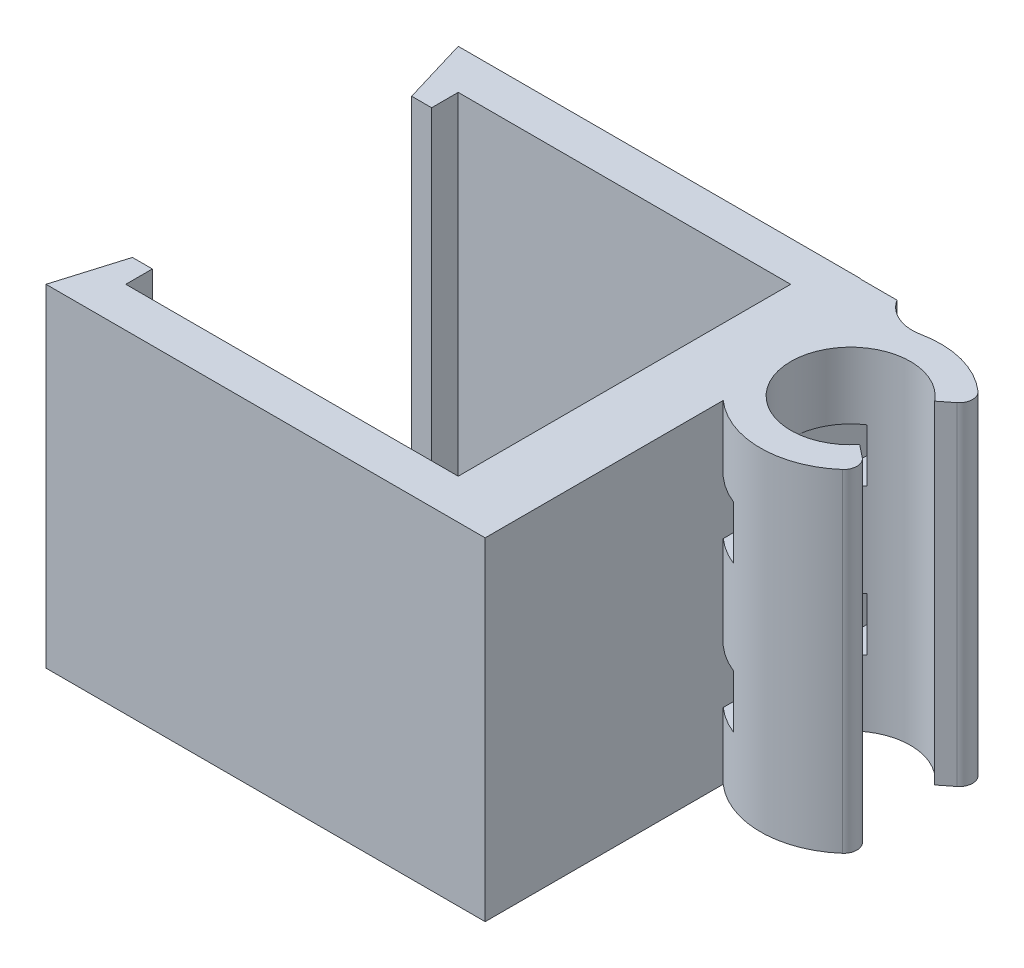
SolidWorks part; units mm, degrees
ref_plane "Спереди" through (0, 0, 0) normal (0, 0, 1) x (1, 0, 0)
ref_plane "Сверху" through (0, 0, 0) normal (0, 1, 0) x (1, 0, 0)
ref_plane "Справа" through (0, 0, 0) normal (1, 0, 0) x (0, 0, -1)
sketch "Эскиз1" plane through (0, 0, 0) normal (0, 1, 0) x (1, 0, 0)
  line L0 (-66.8258, 34.9697) -> (-66.8258, 29.9697)
  line L1 (-63.8258, 29.9697) -> (-63.8258, 31.9697)
  line L2 (-63.8258, 31.9697) -> (-38.8258, 31.9697)
  line L3 (-38.8258, 31.9697) -> (-38.8258, 6.9697)
  line L4 (-38.8258, 6.9697) -> (-63.8258, 6.9697)
  line L5 (-63.8258, 6.9697) -> (-63.8258, 8.9697)
  line L6 (-63.8258, 8.9697) -> (-66.8258, 8.9697)
  line L7 (-66.8258, 8.9697) -> (-66.8258, 3.9697)
  line L8 (-66.8258, 3.9697) -> (-22.1235, 3.9697)
  line L9 (-22.1235, 3.9697) -> (-36.579, 34.9697)
  line L10 (-36.579, 34.9697) -> (-66.8258, 34.9697)
  line L11 (-66.8258, 29.9697) -> (-63.8258, 29.9697)
  dimension "D1" = 25
  dimension "D2" = 25
  dimension "D3" = 25
  dimension "D4" = 155
  dimension "D5" = 3
  dimension "D6" = 3
  dimension "D7" = 3
  dimension "D8" = 3
  dimension "D9" = 2
  dimension "D10" = 2
extrude "Бобышка-Вытянуть1" add sketch "Эскиз1" along normal blind 25
sketch "Эскиз3" plane through (0, 0, 0) normal (0, -1, 0) x (1, 0, 0)
  line L0 (-66.8258, -3.9697) -> (-65.3258, -8.9697)
  line L1 (-63.8258, -8.9697) -> (-66.8258, -8.9697) construction
  line L2 (-65.3258, -8.9697) -> (-66.8258, -8.9697)
  line L3 (-66.8258, -8.9697) -> (-66.8258, -3.9697)
  line L4 (-66.8258, -29.9697) -> (-66.8258, -34.9697)
  line L5 (-66.8258, -34.9697) -> (-65.3258, -29.9697)
  line L6 (-66.8258, -29.9697) -> (-63.8258, -29.9697) construction
  line L7 (-65.3258, -29.9697) -> (-66.8258, -29.9697)
extrude "Вырез-Вытянуть4" cut sketch "Эскиз3" against normal through all
sketch "Эскиз7" plane through (0, 0, 0) normal (0, -1, 0) x (-1, 0, 0)
  line L1 (36.0076, 1.3029) -> (19.3993, 1.3029)
  line L2 (36.0076, 1.3029) -> (36.0076, 39.7765)
  line L3 (36.0076, 39.7765) -> (19.3993, 39.7765)
  line L4 (19.3993, 1.3029) -> (19.3993, 39.7765)
extrude "Вырез-Вытянуть14" cut sketch "Эскиз7" against normal through all
sketch "Эскиз8" plane through (0, 0, 0) normal (0, -1, 0) x (-1, 0, 0)
  line L0 (66.8258, 3.9697) -> (36.0076, 3.9697) construction
  line L1 (38.7989, 3.9697) -> (33.7989, 3.9697)
  line L2 (38.7989, 3.9697) -> (38.7989, 34.9383)
  line L3 (38.7989, 34.9383) -> (33.7989, 34.9383)
  line L4 (33.7989, 3.9697) -> (33.7989, 34.9383)
  dimension "D1" = 5
extrude "Бобышка-Вытянуть2" add sketch "Эскиз8" against normal up to surface (25 mm away) up to face at (-54.2963, 25, -20.5678)
sketch "Эскиз9" plane through (0, 0, 0) normal (0, -1, 0) x (1, 0, 0)
  line L0 (-33.7989, -19.454) -> (1.2661, -19.454) construction
  line L1 (-33.7989, -34.9383) -> (-33.7989, -3.9697) construction
  line L2 (-33.7989, -11.954) -> (-5.8657, -11.954) construction
  line L3 (-33.7989, -26.954) -> (-9.7824, -26.954) construction
  line L4 (-29.2989, -3.3613) -> (-29.2989, -35.1038) construction
  line L5 (-25.7989, -3.3613) -> (-25.7989, -35.1038) construction
  line L6 (-24.0009, -3.3613) -> (-24.0009, -34.4935) construction
  line L7 (-25.7989, -9.1217) -> (-24.0009, -7.6955)
  line L8 (-25.7989, -14.7863) -> (-24.0009, -16.2125)
  line L9 (-25.7989, -24.1307) -> (-24.0009, -22.7126)
  line L10 (-25.7989, -29.7773) -> (-24.0009, -31.1954)
  arc A0 (-25.7989, -9.1217) -> (-25.7989, -14.7863) centre (-29.2989, -11.954) ccw
  arc A1 (-25.7989, -24.1307) -> (-25.7989, -29.7773) centre (-29.2989, -26.954) ccw
  arc A2 (-24.0009, -7.6955) -> (-24.0009, -16.2125) centre (-29.2989, -11.954) ccw
  arc A3 (-24.0009, -22.7126) -> (-24.0009, -31.1954) centre (-29.2989, -26.954) ccw
  dimension "D1" = 7.5
  dimension "D2" = 7.5
  dimension "D3" = 4.5
  dimension "D4" = 3.5
extrude "Бобышка-Вытянуть3" add sketch "Эскиз9" against normal up to surface (25 mm away) up to face at (-52.7142, 25, -21.6795)
fillet "Скругление2" radius 3 2 edges at (-33.7989, 12.5, -6.8594) (-33.7989, 12.5, -32.0343)
fillet "Скругление4" radius 1 4 edges at (-24.0009, 12.5, -7.6955) (-24.0009, 12.5, -16.2125) (-24.0009, 12.5, -31.1954) (-24.0009, 12.5, -22.7126)
sketch "Эскиз10" plane through (0, 0, -3.9697) normal (0, 0, 1) x (1, 0, 0)
  line L0 (-33.7989, 25) -> (-33.7989, 0) construction
  line L1 (-33.7989, 20) -> (-31.7989, 20)
  line L2 (-33.7989, 20) -> (-33.7989, 16)
  line L3 (-33.7989, 16) -> (-31.7989, 16)
  line L4 (-31.7989, 20) -> (-31.7989, 16)
  line L5 (-66.8258, 25) -> (-33.7989, 25) construction
  line L6 (-33.7989, 9) -> (-31.7989, 9)
  line L7 (-33.7989, 9) -> (-33.7989, 5)
  line L8 (-33.7989, 5) -> (-31.7989, 5)
  line L9 (-31.7989, 9) -> (-31.7989, 5)
  line L10 (-66.8258, 0) -> (-33.7989, 0) construction
  dimension "D1" = 2
  dimension "D2" = 2
  dimension "D3" = 4
  dimension "D4" = 4
  dimension "D5" = 5
  dimension "D6" = 5
extrude "Вырез-Вытянуть15" cut sketch "Эскиз10" against normal through all
sketch "Эскиз11" plane through (0, 0, 0) normal (0, -1, 0) x (1, 0, 0)
  line L1 (-33.7989, -3.9697) -> (-23.4418, -3.9697)
  line L2 (-33.7989, -3.9697) -> (-33.7989, -19.9895)
  line L3 (-33.7989, -19.9895) -> (-23.4418, -19.9895)
  line L4 (-23.4418, -3.9697) -> (-23.4418, -19.9895)
extrude "Вырез-Вытянуть16" cut sketch "Эскиз11" against normal through all
